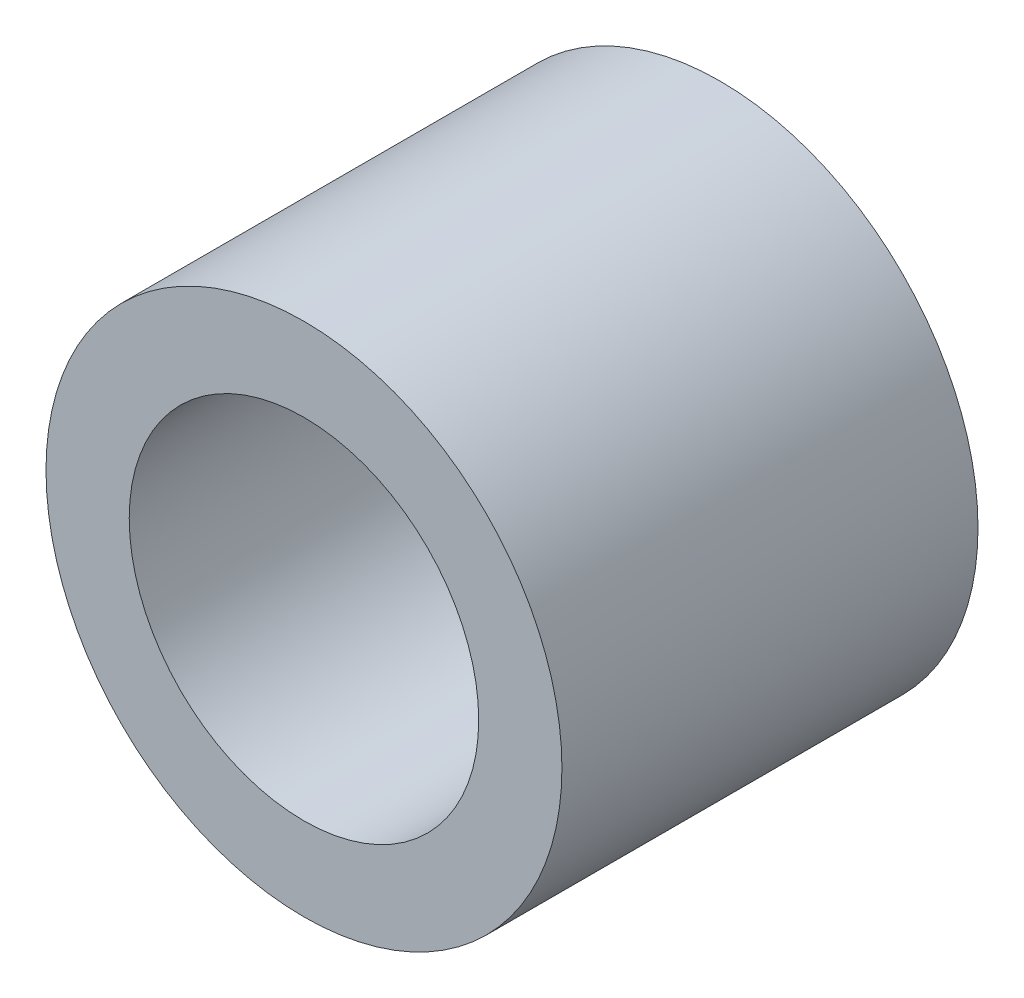
SolidWorks part; units mm, degrees
ref_plane "Front Plane" through (0, 0, 0) normal (0, 0, 1) x (1, 0, 0)
ref_plane "Top Plane" through (0, 0, 0) normal (0, 1, 0) x (1, 0, 0)
ref_plane "Right Plane" through (0, 0, 0) normal (1, 0, 0) x (0, 0, -1)
sketch "Sketch1" plane through (0, 0, 0) normal (0, 0, 1) x (1, 0, 0)
  circle A0 centre (0, 0) radius 2.1
  circle A1 centre (0, 0) radius 3.1
  dimension "D1" = 6.2
  dimension "D2" = 4.2
extrude "Boss-Extrude1" add sketch "Sketch1" along normal mid plane 5
equation "\"ID\"= 4.2"
equation "\"OD\"= 6.2"
equation "\"height\" = 5"
equation "\"D1@Sketch1\"=\"OD\""
equation "\"D2@Sketch1\"=\"ID\""
equation "\"D1@Boss-Extrude1\"=\"height\""
